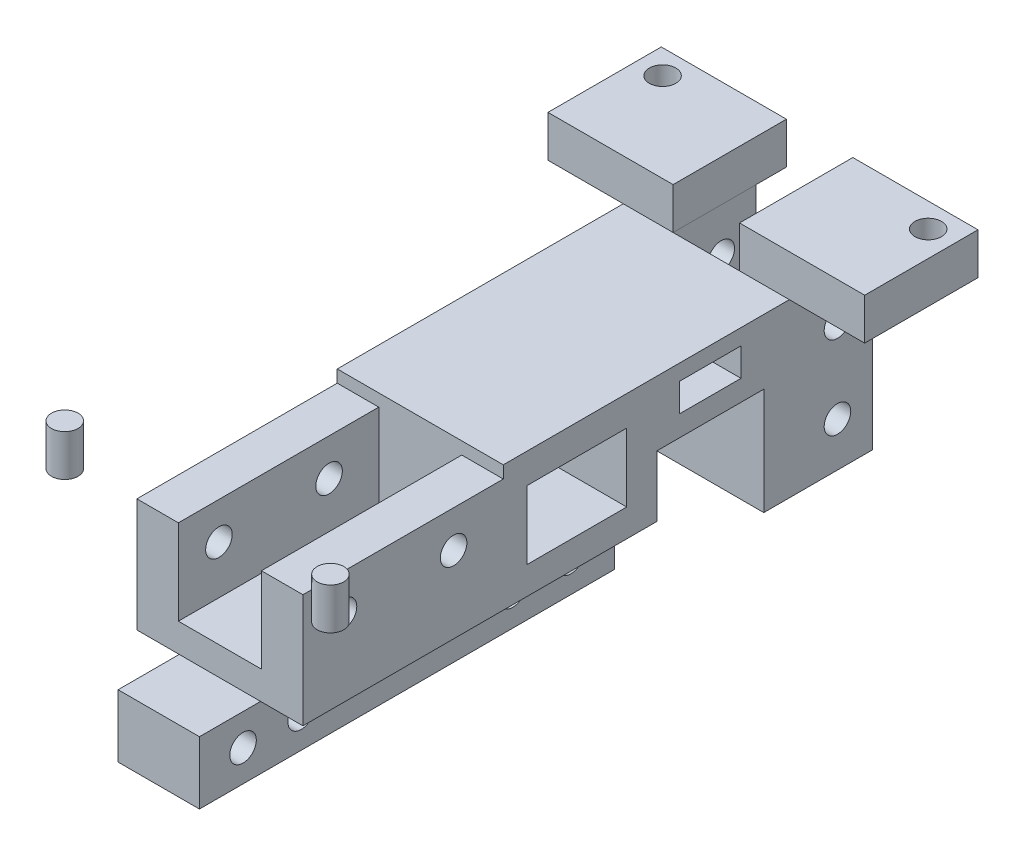
SolidWorks part; units mm, degrees
ref_plane "前视基准面" through (0, 0, 0) normal (0, 0, 1) x (1, 0, 0)
ref_plane "上视基准面" through (0, 0, 0) normal (0, 1, 0) x (1, 0, 0)
ref_plane "右视基准面" through (0, 0, 0) normal (1, 0, 0) x (0, 0, -1)
sketch "草图2" plane through (0, 0, 0) normal (1, 0, 0) x (0, 0, -1)
  line L0 (7, 0) -> (32.5, 0) construction
  line L2 (44.75, 3.775) -> (-5.25, 3.775)
  line L3 (44.75, 3.775) -> (44.75, -3.775)
  line L4 (44.75, -3.775) -> (-5.25, -3.775)
  line L5 (-5.25, 3.775) -> (-5.25, -3.775)
  line L6 (44.75, 3.775) -> (-5.25, -3.775) construction
  line L7 (44.75, -3.775) -> (-5.25, 3.775) construction
  circle A0 centre (0, 0) radius 1.6
  circle A1 centre (7, 0) radius 1.6
  circle A2 centre (32.5, 0) radius 1.6
  circle A3 centre (39.5, 0) radius 1.6
  point P9 (19.75, 0)
extrude "凸台-拉伸1" add sketch "草图2" along normal mid plane 9.8
sketch "草图3" plane through (0, 0, 0) normal (1, 0, 0) x (0, 0, -1)
  line L0 (7, 13) -> (20.26, 13) construction
  line L1 (2.1144, 3.775) -> (2.1144, 17.4551)
  line L2 (44.75, 3.775) -> (-5.25, 3.775) construction
  line L3 (2.1144, 17.4551) -> (26.2473, 17.4551)
  line L4 (26.2473, 17.4551) -> (26.2473, 3.775)
  line L5 (26.2473, 3.775) -> (2.1144, 3.775)
  circle A0 centre (7, 13) radius 1.6
  circle A1 centre (20.26, 13) radius 1.6
  point P0 (7, 0)
  point P6 (13.63, 13)
extrude "凸台-拉伸2" add sketch "草图3" along normal mid plane 20
sketch "草图4" plane through (0, 0, -2.1144) normal (0, 0, 1) x (1, 0, 0)
  line L0 (10, 17.4551) -> (-10, 17.4551) construction
  line L1 (5, 7.1905) -> (-5, 7.1905)
  line L2 (5, 7.1905) -> (5, 17.4551)
  line L3 (5, 17.4551) -> (-5, 17.4551)
  line L4 (-5, 7.1905) -> (-5, 17.4551)
  line L5 (5, 7.1905) -> (-5, 17.4551) construction
  line L6 (5, 17.4551) -> (-5, 7.1905) construction
  point P0 (0, 12.3228)
extrude "切除-拉伸1" cut sketch "草图4" against normal through all
sketch "草图6" plane through (0, 0, 0) normal (1, 0, 0) x (0, 0, -1)
  line L0 (66.5, 3.6) -> (66.5, 13.6) construction
  line L1 (66.5, 8.6) -> (56.4496, 8.6) construction
  line L2 (70.7021, -1.739) -> (57.626, -1.739)
  line L3 (70.7021, -1.739) -> (70.7021, 18.939)
  line L4 (70.7021, 18.939) -> (57.626, 18.939)
  line L5 (57.626, -1.739) -> (57.626, 18.939)
  line L6 (70.7021, -1.739) -> (57.626, 18.939) construction
  line L7 (70.7021, 18.939) -> (57.626, -1.739) construction
  circle A0 centre (66.5, 3.6) radius 1.6
  circle A1 centre (66.5, 13.6) radius 1.6
  point P4 (66.5, 8.6)
  point P9 (64.1641, 8.6)
extrude "凸台-拉伸4" add sketch "草图6" along normal mid plane 20 separate body
sketch "草图7" plane through (0, 0, -70.7021) normal (0, 0, 1) x (1, 0, 0)
  line L0 (10, 18.939) -> (-10, 18.939) construction
  line L1 (-4, 18.939) -> (4, 18.939)
  line L2 (-4, 18.939) -> (-4, -1.739)
  line L3 (-4, -1.739) -> (4, -1.739)
  line L4 (4, 18.939) -> (4, -1.739)
  line L5 (10, -1.739) -> (-10, -1.739) construction
extrude "切除-拉伸2" cut sketch "草图7" along normal blind 10
sketch "草图8" plane through (0, 0, 0) normal (1, 0, 0) x (0, 0, -1)
  line L0 (26.2473, 3.775) -> (26.2473, 17.4551) construction
  line L1 (57.626, 18.939) -> (26.2473, 18.939)
  line L2 (57.626, 18.939) -> (57.626, 11.1399)
  line L3 (57.626, 11.1399) -> (44.75, 11.1399)
  line L4 (26.2473, 18.939) -> (26.2473, 11.1399)
  line L7 (26.2473, 11.1399) -> (26.2473, 3.775)
  line L8 (26.2473, 3.775) -> (44.75, 3.775)
  line L9 (44.75, 11.1399) -> (44.75, 3.775)
extrude "凸台-拉伸5" add sketch "草图8" along normal mid plane 20
sketch "草图9" plane through (10, 0, 0) normal (1, 0, 0) x (0, 0, -1)
  line L1 (29.0864, 15.338) -> (41.1155, 15.338)
  line L2 (29.0864, 15.338) -> (29.0864, 7.1034)
  line L3 (29.0864, 7.1034) -> (41.1155, 7.1034)
  line L4 (41.1155, 15.338) -> (41.1155, 7.1034)
  line L5 (29.0864, 15.338) -> (41.1155, 7.1034) construction
  line L6 (29.0864, 7.1034) -> (41.1155, 15.338) construction
  line L7 (54.8802, 13.6426) -> (47.4529, 13.6426)
  line L8 (54.8802, 13.6426) -> (54.8802, 17.0334)
  line L9 (54.8802, 17.0334) -> (47.4529, 17.0334)
  line L10 (47.4529, 13.6426) -> (47.4529, 17.0334)
  line L11 (54.8802, 13.6426) -> (47.4529, 17.0334) construction
  line L12 (54.8802, 17.0334) -> (47.4529, 13.6426) construction
  point P0 (35.101, 11.2207)
  point P8 (51.1666, 15.338)
extrude "切除-拉伸3" cut sketch "草图9" against normal through all
sketch "草图5" plane through (0, 0, 0) normal (0, 1, 0) x (1, 0, 0)
  line L0 (0, 14.1785) -> (0, 53.7814) construction
  line L2 (16, 71.43) -> (-16, 71.43) construction
  line L3 (16, 71.43) -> (16, -0.57) construction
  line L4 (16, -0.57) -> (-16, -0.57) construction
  line L5 (-16, 71.43) -> (-16, -0.57) construction
  line L6 (16, 71.43) -> (-16, -0.57) construction
  line L7 (16, -0.57) -> (-16, 71.43) construction
  line L12 (-4, 74.3526) -> (-19.0736, 74.3526)
  line L13 (4, 60.7021) -> (19.0736, 60.7021)
  line L14 (4, 60.7021) -> (4, 74.3526)
  line L15 (4, 74.3526) -> (19.0736, 74.3526)
  line L16 (19.0736, 60.7021) -> (19.0736, 74.3526)
  line L17 (-19.0736, 60.7021) -> (-19.0736, 74.3526)
  line L18 (-4, 60.7021) -> (-19.0736, 60.7021)
  line L19 (-4, 60.7021) -> (-4, 74.3526)
  circle A0 centre (-16, 71.43) radius 1.6
  circle A1 centre (16, 71.43) radius 1.6
  circle A2 centre (-16, -0.57) radius 1.6
  circle A3 centre (16, -0.57) radius 1.6
  point P1 (0, 35.43)
extrude "凸台-拉伸3" add sketch "草图5" along normal blind 5 from surface separate body starting at face at (0, 18.939, -57.0884)
